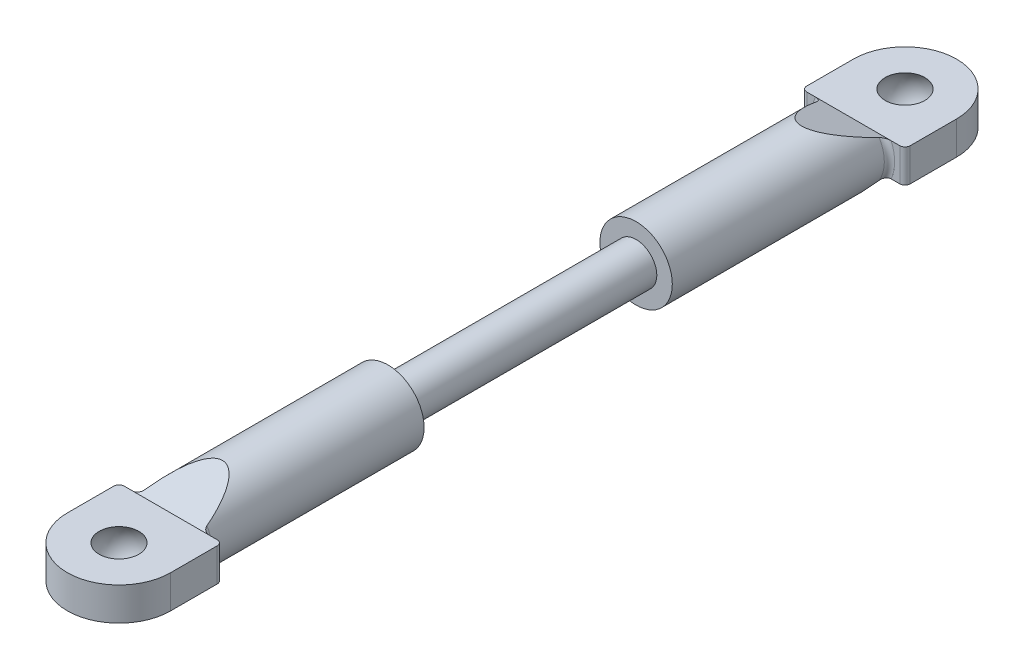
SolidWorks part; units mm, degrees
ref_plane "Front Plane" through (0, 0, 0) normal (0, 0, 1) x (1, 0, 0)
ref_plane "Top Plane" through (0, 0, 0) normal (0, 1, 0) x (1, 0, 0)
ref_plane "Right Plane" through (0, 0, 0) normal (1, 0, 0) x (0, 0, -1)
sketch "Sketch1" plane through (0, 0, 0) normal (0, 0, 1) x (1, 0, 0)
  circle A0 centre (0, 0) radius 2
  dimension "D1" = 4
extrude "Screw Section" add sketch "Sketch1" along normal blind 12 contours A0
sketch "Sketch2" plane through (0, 0, 12) normal (0, 0, 1) x (1, 0, 0)
  circle A0 centre (0, 0) radius 3.5
  dimension "D1" = 7
extrude "Bar Section" add sketch "Sketch2" along normal blind 21
sketch "Sketch3" plane through (0, 0, 0) normal (0, 1, 0) x (1, 0, 0)
  line L0 (5, -33) -> (-5, -33)
  line L1 (-5, -33) -> (-5, -38)
  line L2 (5, -33) -> (5, -38)
  line L3 (-3.5, -33) -> (3.5, -33) construction
  arc A0 (-5, -38) -> (5, -38) centre (0, -38) ccw
  point P4 (0, -43)
  dimension "D1" = 5
  dimension "D2" = 10
  dimension "D3" = 10
extrude "Mount Section" add sketch "Sketch3" along normal mid plane 3.2
sketch "Sketch4" plane through (0, 0, 0) normal (1, 0, 0) x (0, 0, -1)
  line L0 (-28, -3.5) -> (-33, -1.6)
  line L1 (-33, -3.5) -> (-12, -3.5) construction
  line L2 (-33, -1.6) -> (-33, -3.5)
  line L3 (-33, -1.6) -> (-33, -3.5) construction
  line L4 (-33, -3.5) -> (-28, -3.5)
  line L5 (-28, 3.5) -> (-33, 1.6)
  line L6 (-33, 3.5) -> (-33, 1.6) construction
  line L7 (-33, 3.5) -> (-28, 3.5)
  line L9 (-33, 1.6) -> (-33, 3.5)
  dimension "D1" = 5
  dimension "D2" = 1.9
extrude "Bar Taper" cut sketch "Sketch4" against normal through all both and the other way through all
fillet "Mount Fillet" radius 0.5 4 edges at (-5, 0, 33) (-3.5, 0, 33) (5, 0, 33) (3.5, 0, 33)
sketch "Sketch6" plane through (0, 0, 0) normal (1, 0, 0) x (0, 0, -1)
  line L0 (-38, 1.6) -> (-38, -1.6) construction
  line L1 (-43, -1.6) -> (-38, -1.6) construction
  line L2 (-38, 1.6) -> (-43, 1.6) construction
  line L4 (-39.9209, -1.6) -> (-38, -1.6)
  line L5 (-38, -1.6) -> (-38, 1.6)
  line L6 (-38, 1.6) -> (-39.9209, 1.6)
  arc A0 (-39.9209, -1.6) -> (-39.9209, 1.6) centre (-38, 0) cw
  dimension "D1" = 2.5
revolve "Ball Hole" cut sketch "Sketch6" angle 360 about L5
mirror "Mirror" about plane through (0, 0, 0) normal (0, 0, 1) of "Ball Hole", "Bar Section", "Bar Taper", "Mount Section", "Mount Fillet", "Screw Section"
ref_point "Point1"
ref_point "Point2"
